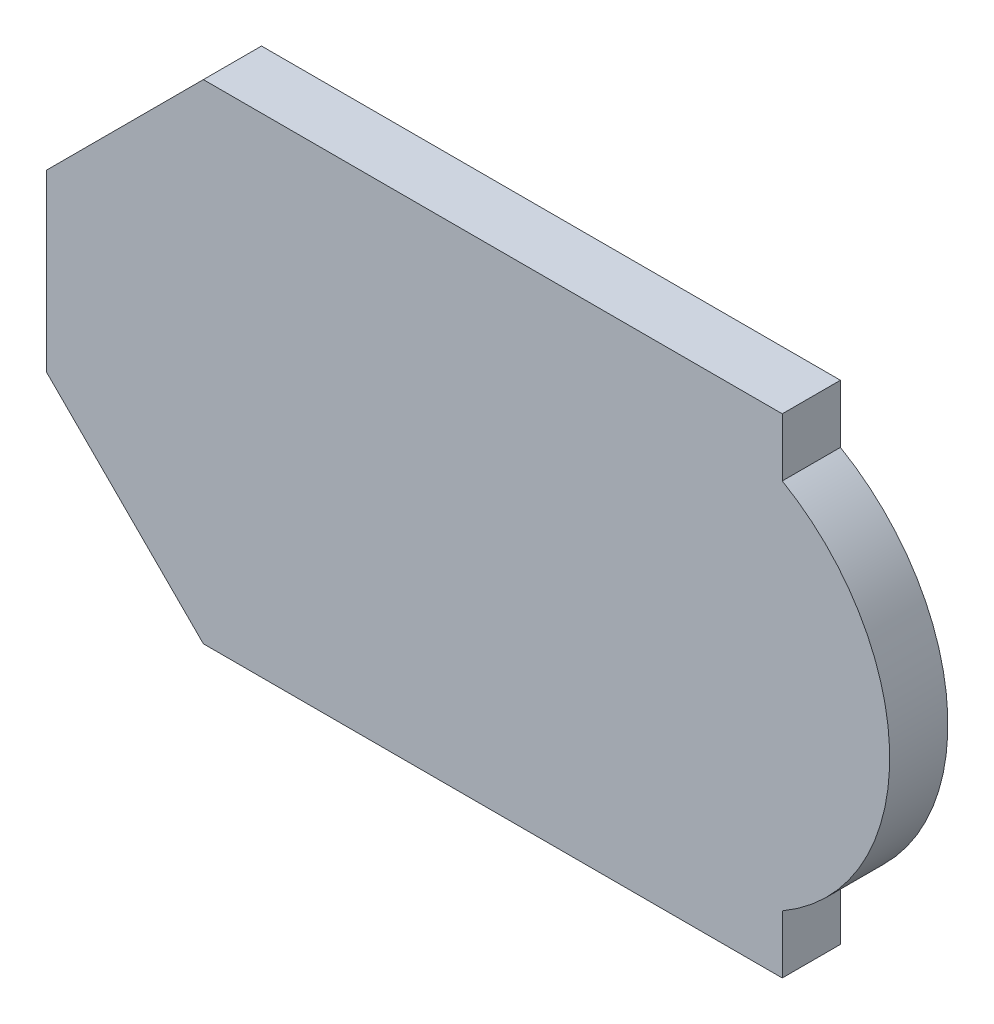
SolidWorks part; units mm, degrees
note: The reader was unsure of these and kept them because the rebuilt part matched: thickness of "Базовая кромка1", "Листовой металл3".
material "AISI 1020"
ref_plane "Спереди" through (0, 0, 0) normal (0, 0, 1) x (1, 0, 0)
ref_plane "Сверху" through (0, 0, 0) normal (0, 1, 0) x (1, 0, 0)
ref_plane "Справа" through (0, 0, 0) normal (1, 0, 0) x (0, 0, -1)
sketch "Эскиз1" plane through (0, 0, 0) normal (0, 0, 1) x (1, 0, 0)
  line L0 (-935, 0) -> (49065, 0) construction
  line L3 (39, 0) -> (29.7624, 16) construction
  line L4 (29.7624, 16) -> (20.5248, 0) construction
  line L5 (65, 16) -> (0, 16) construction
  line L6 (29.7624, 16) -> (29.7624, 21)
  line L7 (29.7624, 21) -> (-20, 21)
  line L8 (-33.5, 7.5) -> (-33.5, -7.5)
  line L9 (-33.5, 7.5) -> (-20, 21)
  line L10 (0, 16) -> (0, -16) construction
  line L11 (29.7624, -16) -> (29.7624, -21)
  line L12 (29.7624, -21) -> (-20, -21)
  line L13 (-33.5, -7.5) -> (-20, -21)
  arc A0 (29.7624, -16) -> (29.7624, 16) centre (20.5248, 0) ccw
  arc A2 (49.3787, 3.4604) -> (74.4853, -12.8852) centre (65, 0) ccw construction
  point P22 (-33.5, 0)
  dimension "D1" = 10
  dimension "D2" = 5
  dimension "D3" = 15
  dimension "D4" = 20
  dimension "45" = 45
base flange "Базовая кромка1" sketch "Эскиз1" thickness 5 reverse thickness direction no parameters "D1"=0.74
sketch "Сгиб-Линии1" [suppressed] plane through (0, 0, 0) normal (0, 1, 0) x (1, 0, 0)
sketch "Граничная рамка1" [suppressed] plane through (0, 0, 0) normal (0, 1, 0) x (1, 0, 0)
sheet metal parameters "Листовой металл3" thickness 5 parameters "D1"=0.74, "D7"=4
flat pattern "Развертка3" [suppressed]
sketch "Сгиб-Линии2" plane through (0, 0, 0) normal (0, 1, 0) x (1, 0, 0)
sketch3d "Граничная рамка2" [suppressed]
  line L0 (-54.0248, 21, 0) -> (18.4751, 21, 0) construction
  line L1 (-54.0248, -21, 0) -> (18.4751, -21, 0) construction
  line L2 (-54.0248, 21, 0) -> (-54.0248, -21, 0) construction
  line L3 (18.4751, 21, 0) -> (18.4751, -21, 0) construction
